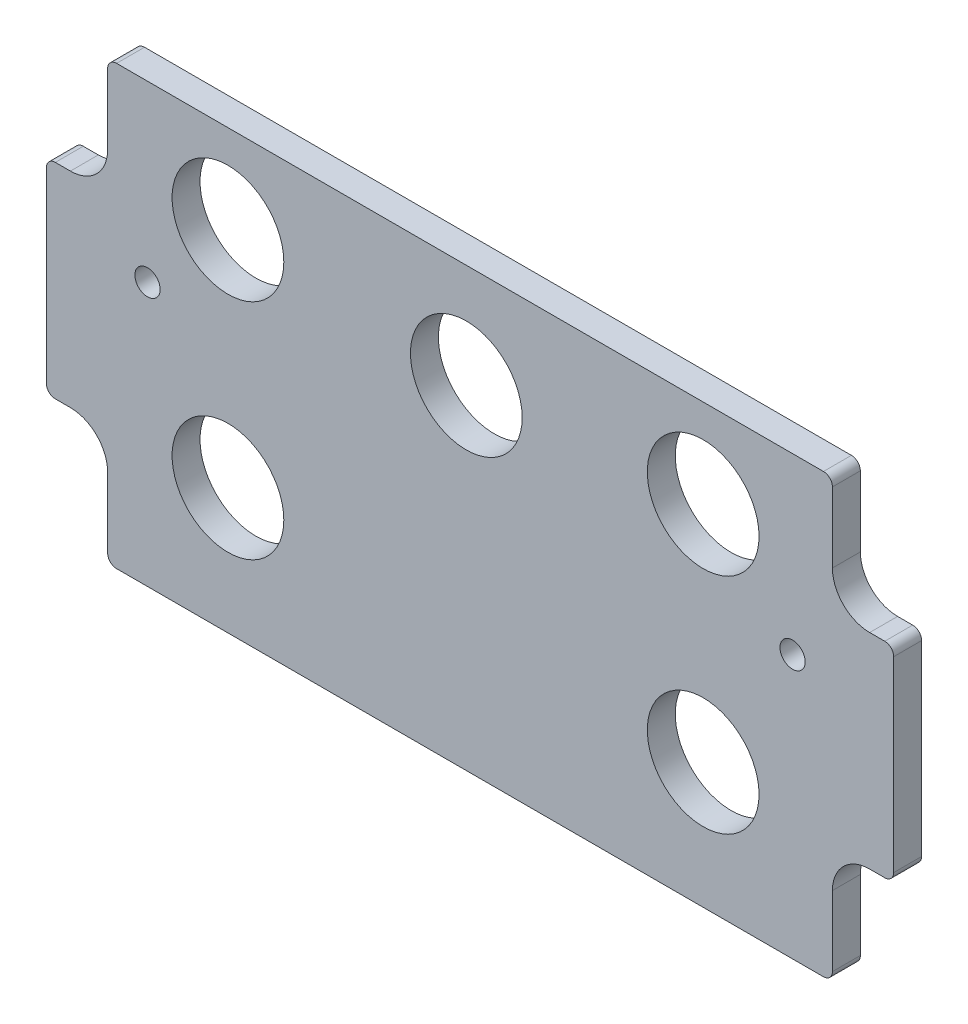
SolidWorks part; units mm, degrees
ref_plane "Front Plane" through (0, 0, 0) normal (0, 0, 1) x (1, 0, 0)
ref_plane "Top Plane" through (0, 0, 0) normal (0, 1, 0) x (1, 0, 0)
ref_plane "Right Plane" through (0, 0, 0) normal (1, 0, 0) x (0, 0, -1)
sketch "Sketch1" plane through (0, 0, 0) normal (0, 0, 1) x (1, 0, 0)
  line L12 (134.8105, 61.9125) -> (134.8105, 73.8822)
  line L13 (133.2865, 75.4062) -> (12.7635, 75.4062)
  line L14 (11.2395, 73.8822) -> (11.2395, 61.9125)
  line L15 (4.8895, 55.5625) -> (2.3178, 55.5625)
  line L16 (0.7938, 54.0385) -> (0.7938, 22.1615)
  line L17 (2.3178, 20.6375) -> (4.8895, 20.6375)
  line L18 (11.2395, 14.2875) -> (11.2395, 2.3178)
  line L19 (12.7635, 0.7938) -> (133.2865, 0.7937)
  line L20 (134.8105, 2.3177) -> (134.8105, 14.2875)
  line L21 (141.1605, 20.6375) -> (143.7323, 20.6375)
  line L22 (145.2563, 22.1615) -> (145.2563, 54.0385)
  line L23 (143.7323, 55.5625) -> (141.1605, 55.5625)
  line L24 (134.8105, 61.9125) -> (134.8105, 73.8822)
  line L25 (133.2865, 75.4062) -> (12.7635, 75.4062)
  line L26 (11.2395, 73.8822) -> (11.2395, 61.9125)
  line L27 (4.8895, 55.5625) -> (2.3178, 55.5625)
  line L28 (0.7938, 54.0385) -> (0.7938, 22.1615)
  line L29 (2.3178, 20.6375) -> (4.8895, 20.6375)
  line L30 (11.2395, 14.2875) -> (11.2395, 2.3178)
  line L31 (12.7635, 0.7938) -> (133.2865, 0.7937)
  line L32 (134.8105, 2.3177) -> (134.8105, 14.2875)
  line L33 (141.1605, 20.6375) -> (143.7323, 20.6375)
  line L34 (145.2563, 22.1615) -> (145.2563, 54.0385)
  line L35 (143.7323, 55.5625) -> (141.1605, 55.5625)
  arc A12 (134.8105, 61.9125) -> (141.1605, 55.5625) centre (141.1605, 61.9125) ccw
  arc A13 (134.8105, 73.8822) -> (133.2865, 75.4062) centre (133.2865, 73.8822) ccw
  arc A14 (12.7635, 75.4062) -> (11.2395, 73.8822) centre (12.7635, 73.8822) ccw
  arc A15 (4.8895, 55.5625) -> (11.2395, 61.9125) centre (4.8895, 61.9125) ccw
  arc A16 (2.3178, 55.5625) -> (0.7938, 54.0385) centre (2.3178, 54.0385) ccw
  arc A17 (0.7938, 22.1615) -> (2.3178, 20.6375) centre (2.3178, 22.1615) ccw
  arc A18 (11.2395, 14.2875) -> (4.8895, 20.6375) centre (4.8895, 14.2875) ccw
  arc A19 (11.2395, 2.3178) -> (12.7635, 0.7938) centre (12.7635, 2.3178) ccw
  arc A20 (133.2865, 0.7937) -> (134.8105, 2.3177) centre (133.2865, 2.3177) ccw
  arc A21 (141.1605, 20.6375) -> (134.8105, 14.2875) centre (141.1605, 14.2875) ccw
  arc A22 (143.7323, 20.6375) -> (145.2563, 22.1615) centre (143.7323, 22.1615) ccw
  arc A23 (145.2563, 54.0385) -> (143.7323, 55.5625) centre (143.7323, 54.0385) ccw
  arc A24 (134.8105, 61.9125) -> (141.1605, 55.5625) centre (141.1605, 61.9125) ccw
  arc A25 (134.8105, 73.8822) -> (133.2865, 75.4062) centre (133.2865, 73.8822) ccw
  arc A26 (12.7635, 75.4062) -> (11.2395, 73.8822) centre (12.7635, 73.8822) ccw
  arc A27 (4.8895, 55.5625) -> (11.2395, 61.9125) centre (4.8895, 61.9125) ccw
  arc A28 (2.3178, 55.5625) -> (0.7938, 54.0385) centre (2.3178, 54.0385) ccw
  arc A29 (0.7938, 22.1615) -> (2.3178, 20.6375) centre (2.3178, 22.1615) ccw
  arc A30 (11.2395, 14.2875) -> (4.8895, 20.6375) centre (4.8895, 14.2875) ccw
  arc A31 (11.2395, 2.3178) -> (12.7635, 0.7938) centre (12.7635, 2.3178) ccw
  arc A32 (133.2865, 0.7937) -> (134.8105, 2.3177) centre (133.2865, 2.3177) ccw
  arc A33 (141.1605, 20.6375) -> (134.8105, 14.2875) centre (141.1605, 14.2875) ccw
  arc A34 (143.7323, 20.6375) -> (145.2563, 22.1615) centre (143.7323, 22.1615) ccw
  arc A35 (145.2563, 54.0385) -> (143.7323, 55.5625) centre (143.7323, 54.0385) ccw
  dimension "D1" = 0
extrude "Boss-Extrude1" add sketch "Sketch1" along normal blind 4.7625
hole_wizard "3/4 (0.75) Diameter Hole1" positions "Sketch3" profile "Sketch2" hole size "3/4" standard "ANSI Inch" end condition through all
sketch "Sketch3" plane through (0, 0, 4.7625) normal (0, 0, 1) x (1, 0, 0)
  point P0 (31.75, 60.325)
  point P4 (72.39, 57.658)
  point P7 (112.776, 60.325)
  point P10 (112.776, 22.225)
  point P13 (31.75, 22.225)
sketch "Sketch2" plane through (31.75, 60.325, 4.7625) normal (1, 0, 0) x (0, -1, 0)
  line L0 (0, 0) -> (0, 4.7625)
  line L1 (0, 4.7625) -> (9.525, 4.7625)
  line L2 (9.525, 4.7625) -> (9.525, 0)
  line L5 (9.525, 0) -> (0, 0)
  line L11 (0, -6.35) -> (0, 107.95) construction
  dimension "Thru Hole Dia." = 19.05
  dimension "Thru Hole Depth" = 4.7625
hole_wizard "#6 Clearance Hole1" positions "Sketch5" profile "Sketch4" hole size "#6" standard "ANSI Inch" end condition through all
sketch "Sketch5" plane through (0, 0, 4.7625) normal (0, 0, 1) x (1, 0, 0)
  point P0 (18.034, 45.72)
  point P3 (128.016, 45.72)
sketch "Sketch4" plane through (18.034, 45.72, 4.7625) normal (1, 0, 0) x (0, -1, 0)
  line L0 (0, 0) -> (0, 4.7625)
  line L1 (0, 4.7625) -> (2.1526, 4.7625)
  line L2 (2.1526, 4.7625) -> (2.1526, 0)
  line L5 (2.1526, 0) -> (0, 0)
  line L11 (0, -6.35) -> (0, 107.95) construction
  dimension "Thru Hole Dia." = 4.3053
  dimension "Thru Hole Depth" = 4.7625
